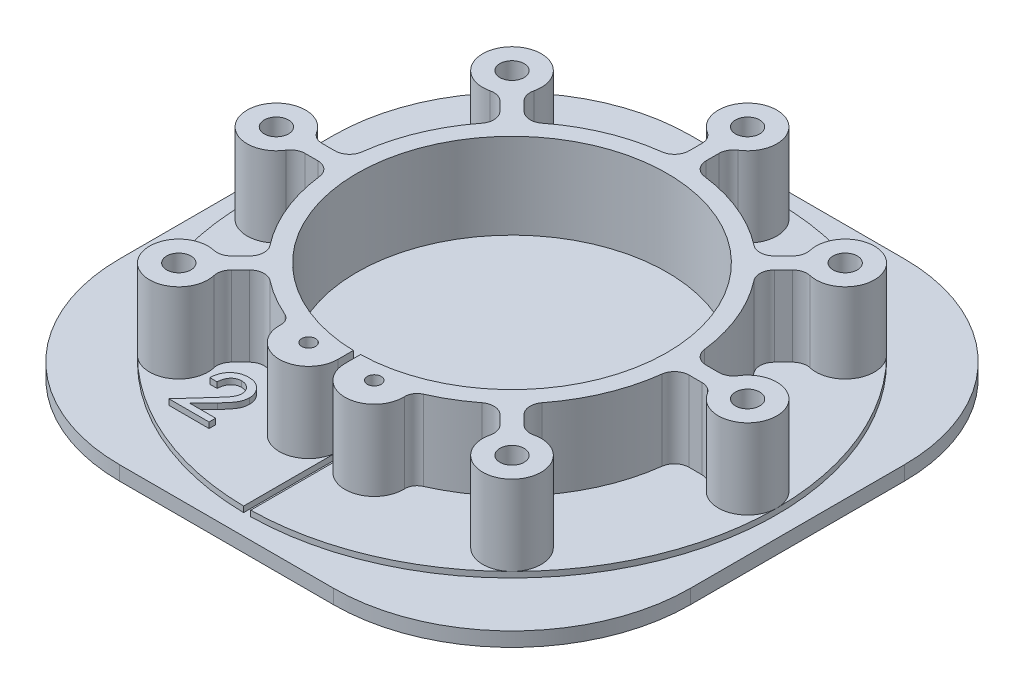
SolidWorks part; units mm, degrees
other "rim"
other "bottom"
ref_plane "Front Plane" through (0, 0, 0) normal (0, 0, 1) x (1, 0, 0)
ref_plane "Top Plane" through (0, 0, 0) normal (0, 1, 0) x (1, 0, 0)
ref_plane "Right Plane" through (0, 0, 0) normal (1, 0, 0) x (0, 0, -1)
ref_axis "Axis1" through (0, -8, 0) along (0, 1, 0)
ref_plane "Plane1" through (0, -11, 0) normal (0, -1, 0) x (-1, 0, 0)
sketch "Sketch1" plane through (0, -11, 0) normal (0, -1, 0) x (-1, 0, 0)
  line L1 (-40, -40) -> (40, -40)
  line L2 (-40, -40) -> (-40, 40)
  line L3 (-40, 40) -> (40, 40)
  line L4 (40, -40) -> (40, 40)
  line L5 (0, 40) -> (0, -40) construction
  line L6 (-40, 0) -> (40, 0) construction
  circle A0 centre (-8, 8) radius 2.25 construction
  circle A1 centre (8, 8) radius 2.25 construction
  circle A2 centre (8, -8) radius 2.25 construction
  circle A3 centre (-8, -8) radius 2.25 construction
  point P0 (0, 0)
  dimension "D2" = 4.5
  dimension "D1" = 80
extrude "Boss-Extrude1" add sketch "Sketch1" along normal blind 2
sketch "Sketch2" plane through (0, -11, 0) normal (0, 1, 0) x (1, 0, 0)
  line L0 (-0.5, -21.7443) -> (-0.5, -23.9116)
  line L1 (0.5, -21.7443) -> (0.5, -23.9116)
  line L2 (-0.5, -21.7443) -> (0.5, -21.7443) construction
  line L3 (0, -1000) -> (0, 49000) construction
  line L4 (-1.2, 27.8087) -> (-1.2, 26.0239)
  line L5 (1.2, 27.8087) -> (1.2, 26.0239)
  line L7 (-20.5122, 18.8152) -> (-19.2502, 17.5531)
  line L8 (-18.8152, 20.5122) -> (-17.5531, 19.2502)
  line L9 (-27.8087, -1.2) -> (-26.0239, -1.2)
  line L10 (-27.8087, 1.2) -> (-26.0239, 1.2)
  line L11 (-18.8152, -20.5122) -> (-17.5531, -19.2502)
  line L12 (-20.5122, -18.8152) -> (-19.2502, -17.5531)
  line L13 (40, 0) -> (-40, 0) construction
  line L14 (18.8152, -20.5122) -> (17.5531, -19.2502)
  line L15 (20.5122, -18.8152) -> (19.2502, -17.5531)
  line L16 (1.2, 27.8087) -> (1.2, 26.0239)
  line L17 (0.5, -21.7443) -> (0.5, -23.9116)
  line L18 (27.8087, 1.2) -> (26.0239, 1.2)
  line L19 (27.8087, -1.2) -> (26.0239, -1.2)
  line L20 (18.8152, 20.5122) -> (17.5531, 19.2502)
  line L21 (20.5122, 18.8152) -> (19.2502, 17.5531)
  circle A0 centre (0, 0) radius 21.75 construction
  arc A1 (-0.5, -21.7443) -> (0.5, -21.7443) centre (0, 0) cw
  circle A3 centre (-4.6, -23.9116) radius 1.7 construction
  circle A4 centre (-4.6, -23.9116) radius 4.1 construction
  arc A5 (-0.5, -23.9116) -> (-8.6972, -23.76) centre (-4.6, -23.9116) cw
  arc A6 (-8.6972, -23.76) -> (-9.7121, -22.142) centre (-10.3942, -23.6972) ccw
  arc A7 (-2.1658, 29.547) -> (2.1658, 29.547) centre (0, 33.0283) cw
  circle A8 centre (0, 33.0283) radius 1.7
  arc A9 (-2.1658, 29.547) -> (-1.2, 27.8087) centre (-3.2473, 27.8087) cw
  arc A10 (2.1658, 29.547) -> (1.2, 27.8087) centre (3.2473, 27.8087) ccw
  arc A11 (-1.2, 26.0239) -> (-2.9938, 23.9923) centre (-3.2473, 26.0239) cw
  arc A12 (1.2, 26.0239) -> (2.9938, 23.9923) centre (3.2473, 26.0239) ccw
  arc A13 (-22.4244, 19.3614) -> (-19.3614, 22.4244) centre (-23.3545, 23.3545) cw
  circle A14 centre (-23.3545, 23.3545) radius 1.7
  arc A15 (-22.4244, 19.3614) -> (-20.5122, 18.8152) centre (-21.9599, 17.3675) cw
  arc A16 (-19.3614, 22.4244) -> (-18.8152, 20.5122) centre (-17.3675, 21.9599) ccw
  arc A17 (-19.2502, 17.5531) -> (-19.0821, 14.8482) centre (-20.6979, 16.1055) cw
  arc A18 (-17.5531, 19.2502) -> (-14.8482, 19.0821) centre (-16.1055, 20.6979) ccw
  arc A19 (-29.547, -2.1658) -> (-29.547, 2.1658) centre (-33.0283, 0) cw
  circle A20 centre (-33.0283, 0) radius 1.7
  arc A21 (-29.547, -2.1658) -> (-27.8087, -1.2) centre (-27.8087, -3.2473) cw
  arc A22 (-29.547, 2.1658) -> (-27.8087, 1.2) centre (-27.8087, 3.2473) ccw
  arc A23 (-26.0239, -1.2) -> (-23.9923, -2.9938) centre (-26.0239, -3.2473) cw
  arc A24 (-26.0239, 1.2) -> (-23.9923, 2.9938) centre (-26.0239, 3.2473) ccw
  arc A25 (-19.3614, -22.4244) -> (-22.4244, -19.3614) centre (-23.3545, -23.3545) cw
  circle A26 centre (-23.3545, -23.3545) radius 1.7
  arc A27 (-19.3614, -22.4244) -> (-18.8152, -20.5122) centre (-17.3675, -21.9599) cw
  arc A28 (-22.4244, -19.3614) -> (-20.5122, -18.8152) centre (-21.9599, -17.3675) ccw
  arc A29 (-17.5531, -19.2502) -> (-14.8482, -19.0821) centre (-16.1055, -20.6979) cw
  arc A30 (-19.2502, -17.5531) -> (-19.0821, -14.8482) centre (-20.6979, -16.1055) ccw
  arc A31 (-2.9938, 23.9923) -> (-14.8482, 19.0821) centre (0, 0) ccw
  arc A32 (-19.0821, 14.8482) -> (-23.9923, 2.9938) centre (0, 0) ccw
  arc A33 (-23.9923, -2.9938) -> (-19.0821, -14.8482) centre (0, 0) ccw
  arc A34 (-14.8482, -19.0821) -> (-9.7121, -22.142) centre (0, 0) ccw
  arc A35 (19.3614, -22.4244) -> (18.8152, -20.5122) centre (17.3675, -21.9599) ccw
  arc A36 (17.5531, -19.2502) -> (14.8482, -19.0821) centre (16.1055, -20.6979) ccw
  arc A37 (19.2502, -17.5531) -> (19.0821, -14.8482) centre (20.6979, -16.1055) cw
  arc A38 (22.4244, -19.3614) -> (20.5122, -18.8152) centre (21.9599, -17.3675) cw
  arc A39 (2.1658, 29.547) -> (1.2, 27.8087) centre (3.2473, 27.8087) ccw
  arc A40 (1.2, 26.0239) -> (2.9938, 23.9923) centre (3.2473, 26.0239) ccw
  arc A41 (2.9938, 23.9923) -> (14.8482, 19.0821) centre (0, 0) cw
  arc A42 (14.8482, -19.0821) -> (9.7121, -22.142) centre (0, 0) cw
  arc A43 (8.6972, -23.76) -> (9.7121, -22.142) centre (10.3942, -23.6972) cw
  arc A44 (0.5, -23.9116) -> (8.6972, -23.76) centre (4.6, -23.9116) ccw
  circle A45 centre (4.6, -23.9116) radius 1.7 construction
  arc A46 (23.9923, -2.9938) -> (19.0821, -14.8482) centre (0, 0) cw
  arc A47 (19.0821, 14.8482) -> (23.9923, 2.9938) centre (0, 0) cw
  arc A48 (19.3614, -22.4244) -> (22.4244, -19.3614) centre (23.3545, -23.3545) ccw
  arc A49 (26.0239, 1.2) -> (23.9923, 2.9938) centre (26.0239, 3.2473) cw
  arc A50 (26.0239, -1.2) -> (23.9923, -2.9938) centre (26.0239, -3.2473) ccw
  arc A51 (29.547, 2.1658) -> (27.8087, 1.2) centre (27.8087, 3.2473) cw
  arc A52 (29.547, -2.1658) -> (27.8087, -1.2) centre (27.8087, -3.2473) ccw
  circle A53 centre (33.0283, 0) radius 1.7
  arc A54 (29.547, -2.1658) -> (29.547, 2.1658) centre (33.0283, 0) ccw
  arc A55 (17.5531, 19.2502) -> (14.8482, 19.0821) centre (16.1055, 20.6979) cw
  arc A56 (19.2502, 17.5531) -> (19.0821, 14.8482) centre (20.6979, 16.1055) ccw
  arc A57 (19.3614, 22.4244) -> (18.8152, 20.5122) centre (17.3675, 21.9599) cw
  arc A58 (22.4244, 19.3614) -> (20.5122, 18.8152) centre (21.9599, 17.3675) ccw
  circle A59 centre (23.3545, 23.3545) radius 1.7
  arc A60 (22.4244, 19.3614) -> (19.3614, 22.4244) centre (23.3545, 23.3545) ccw
  circle A61 centre (23.3545, -23.3545) radius 1.7
  circle A62 centre (-4.6, -23.9116) radius 0.9685
  circle A63 centre (4.6, -23.9116) radius 0.9685
  point P79 (0, 0)
  dimension "D1" = 43.5
  dimension "D4" = 3.4
  dimension "D3" = 1.937
  dimension "D2" = 1
  dimension "D7" = 2.4
  dimension "D8" = 4
extrude "Boss-Extrude2" add sketch "Sketch2" along normal offset from surface (12 mm away) 1 separate body contours A58 A60 A57 L20 A55 A41 A12 L5 A10 A7 A9 L4 A11 A31 A18 L8 A16 A13 A15 L7 A17 A32 A24 L10 A22 A19 A21 L9 A23 A33 A30 L12 A28 A25 A27 L11 A29 A34 A6 A5 L0 A1 L1 A44 A43 A42 A36 L14 A35 A48 A38 region at (-1.4878, -11, 22.8279) offset beyond the face yes
sketch "Sketch3" plane through (0, -11, 0) normal (0, 1, 0) x (1, 0, 0)
  circle A0 centre (0, 33.0283) radius 1.4
  circle A1 centre (23.3545, 23.3545) radius 1.4
  circle A2 centre (33.0283, 0) radius 1.4
  circle A3 centre (23.3545, -23.3545) radius 1.4
  circle A4 centre (4.6, -23.9116) radius 1.4
  circle A5 centre (-4.6, -23.9116) radius 1.4
  circle A6 centre (-23.3545, -23.3545) radius 1.4
  circle A7 centre (-33.0283, 0) radius 1.4
  circle A8 centre (-23.3545, 23.3545) radius 1.4
  dimension "D1" = 2.8
extrude "Cut-Extrude1" cut sketch "Sketch3" against normal through all
fillet "Fillet1" radius 25 4 edges at (-40, -12, -40) (40, -12, -40) (40, -12, 40) (-40, -12, 40)
sketch "Sketch4" plane through (0, -11, 0) normal (0, 1, 0) x (1, 0, 0)
  line L32 (18.5323, 20.7951) -> (17.2703, 19.533)
  line L33 (1.6, 26.0239) -> (1.6, 27.8087)
  line L34 (-1.6, 27.8087) -> (-1.6, 26.0239)
  line L35 (-17.2703, 19.533) -> (-18.5323, 20.7951)
  line L36 (-20.7951, 18.5323) -> (-19.533, 17.2703)
  line L37 (-26.0239, 1.6) -> (-27.8087, 1.6)
  line L38 (-27.8087, -1.6) -> (-26.0239, -1.6)
  line L39 (-19.533, -17.2703) -> (-20.7951, -18.5323)
  line L40 (-18.5323, -20.7951) -> (-17.2703, -19.533)
  line L41 (17.2703, -19.533) -> (18.5323, -20.7951)
  line L42 (20.7951, -18.5323) -> (19.533, -17.2703)
  line L43 (26.0239, -1.6) -> (27.8087, -1.6)
  line L44 (27.8087, 1.6) -> (26.0239, 1.6)
  line L45 (19.533, 17.2703) -> (20.7951, 18.5323)
  line L46 (18.5323, 20.7951) -> (17.2703, 19.533)
  line L47 (1.6, 26.0239) -> (1.6, 27.8087)
  line L48 (-1.6, 27.8087) -> (-1.6, 26.0239)
  line L49 (-17.2703, 19.533) -> (-18.5323, 20.7951)
  line L50 (-20.7951, 18.5323) -> (-19.533, 17.2703)
  line L51 (-26.0239, 1.6) -> (-27.8087, 1.6)
  line L52 (-27.8087, -1.6) -> (-26.0239, -1.6)
  line L53 (-19.533, -17.2703) -> (-20.7951, -18.5323)
  line L54 (-18.5323, -20.7951) -> (-17.2703, -19.533)
  line L55 (17.2703, -19.533) -> (18.5323, -20.7951)
  line L56 (20.7951, -18.5323) -> (19.533, -17.2703)
  line L57 (26.0239, -1.6) -> (27.8087, -1.6)
  line L58 (27.8087, 1.6) -> (26.0239, 1.6)
  line L59 (19.533, 17.2703) -> (20.7951, 18.5323)
  line L60 (-0.1, -23.9116) -> (-0.1, -21.3498)
  line L61 (-0.1, -23.9116) -> (-0.1, -21.3498)
  line L62 (0.1, -21.3498) -> (0.1, -23.9116)
  line L63 (0.1, -21.3498) -> (0.1, -23.9116)
  arc A96 (22.3336, 18.9719) -> (20.7951, 18.5323) centre (21.9599, 17.3675) ccw
  arc A97 (22.3336, 18.9719) -> (18.9719, 22.3336) centre (23.3545, 23.3545) ccw
  arc A98 (18.5323, 20.7951) -> (18.9719, 22.3336) centre (17.3675, 21.9599) ccw
  arc A99 (15.0938, 19.3978) -> (17.2703, 19.533) centre (16.1055, 20.6979) ccw
  arc A100 (15.0938, 19.3978) -> (3.0434, 24.3892) centre (0, 0) ccw
  arc A101 (1.6, 26.0239) -> (3.0434, 24.3892) centre (3.2473, 26.0239) ccw
  arc A102 (2.3771, 29.2074) -> (1.6, 27.8087) centre (3.2473, 27.8087) ccw
  arc A103 (2.3771, 29.2074) -> (-2.3771, 29.2074) centre (0, 33.0283) ccw
  arc A104 (-1.6, 27.8087) -> (-2.3771, 29.2074) centre (-3.2473, 27.8087) ccw
  arc A105 (-3.0434, 24.3892) -> (-1.6, 26.0239) centre (-3.2473, 26.0239) ccw
  arc A106 (-3.0434, 24.3892) -> (-15.0938, 19.3978) centre (0, 0) ccw
  arc A107 (-17.2703, 19.533) -> (-15.0938, 19.3978) centre (-16.1055, 20.6979) ccw
  arc A108 (-18.9719, 22.3336) -> (-18.5323, 20.7951) centre (-17.3675, 21.9599) ccw
  arc A109 (-18.9719, 22.3336) -> (-22.3336, 18.9719) centre (-23.3545, 23.3545) ccw
  arc A110 (-20.7951, 18.5323) -> (-22.3336, 18.9719) centre (-21.9599, 17.3675) ccw
  arc A111 (-19.3978, 15.0938) -> (-19.533, 17.2703) centre (-20.6979, 16.1055) ccw
  arc A112 (-19.3978, 15.0938) -> (-24.3892, 3.0434) centre (0, 0) ccw
  arc A113 (-26.0239, 1.6) -> (-24.3892, 3.0434) centre (-26.0239, 3.2473) ccw
  arc A114 (-29.2074, 2.3771) -> (-27.8087, 1.6) centre (-27.8087, 3.2473) ccw
  arc A115 (-29.2074, 2.3771) -> (-29.2074, -2.3771) centre (-33.0283, 0) ccw
  arc A116 (-27.8087, -1.6) -> (-29.2074, -2.3771) centre (-27.8087, -3.2473) ccw
  arc A117 (-24.3892, -3.0434) -> (-26.0239, -1.6) centre (-26.0239, -3.2473) ccw
  arc A118 (-24.3892, -3.0434) -> (-19.3978, -15.0938) centre (0, 0) ccw
  arc A119 (-19.533, -17.2703) -> (-19.3978, -15.0938) centre (-20.6979, -16.1055) ccw
  arc A120 (-22.3336, -18.9719) -> (-20.7951, -18.5323) centre (-21.9599, -17.3675) ccw
  arc A121 (-22.3336, -18.9719) -> (-18.9719, -22.3336) centre (-23.3545, -23.3545) ccw
  arc A122 (-18.5323, -20.7951) -> (-18.9719, -22.3336) centre (-17.3675, -21.9599) ccw
  arc A123 (-15.0938, -19.3978) -> (-17.2703, -19.533) centre (-16.1055, -20.6979) ccw
  arc A124 (-15.0938, -19.3978) -> (-9.8727, -22.5084) centre (0, 0) ccw
  arc A125 (-9.0969, -23.7452) -> (-9.8727, -22.5084) centre (-10.3942, -23.6972) ccw
  arc A126 (-9.0969, -23.7452) -> (-0.1, -23.9116) centre (-4.6, -23.9116) ccw
  arc A127 (0.1, -23.9116) -> (9.0969, -23.7452) centre (4.6, -23.9116) ccw
  arc A128 (9.8727, -22.5084) -> (9.0969, -23.7452) centre (10.3942, -23.6972) ccw
  arc A129 (9.8727, -22.5084) -> (15.0938, -19.3978) centre (0, 0) ccw
  arc A130 (17.2703, -19.533) -> (15.0938, -19.3978) centre (16.1055, -20.6979) ccw
  arc A131 (18.9719, -22.3336) -> (18.5323, -20.7951) centre (17.3675, -21.9599) ccw
  arc A132 (18.9719, -22.3336) -> (22.3336, -18.9719) centre (23.3545, -23.3545) ccw
  arc A133 (20.7951, -18.5323) -> (22.3336, -18.9719) centre (21.9599, -17.3675) ccw
  arc A134 (19.3978, -15.0938) -> (19.533, -17.2703) centre (20.6979, -16.1055) ccw
  arc A135 (19.3978, -15.0938) -> (24.3892, -3.0434) centre (0, 0) ccw
  arc A136 (26.0239, -1.6) -> (24.3892, -3.0434) centre (26.0239, -3.2473) ccw
  arc A137 (29.2074, -2.3771) -> (27.8087, -1.6) centre (27.8087, -3.2473) ccw
  arc A138 (29.2074, -2.3771) -> (29.2074, 2.3771) centre (33.0283, 0) ccw
  arc A139 (27.8087, 1.6) -> (29.2074, 2.3771) centre (27.8087, 3.2473) ccw
  arc A140 (24.3892, 3.0434) -> (26.0239, 1.6) centre (26.0239, 3.2473) ccw
  arc A141 (24.3892, 3.0434) -> (19.3978, 15.0938) centre (0, 0) ccw
  arc A142 (19.533, 17.2703) -> (19.3978, 15.0938) centre (20.6979, 16.1055) ccw
  arc A143 (22.3336, 18.9719) -> (20.7951, 18.5323) centre (21.9599, 17.3675) ccw
  arc A144 (22.3336, 18.9719) -> (18.9719, 22.3336) centre (23.3545, 23.3545) ccw
  arc A145 (18.5323, 20.7951) -> (18.9719, 22.3336) centre (17.3675, 21.9599) ccw
  arc A146 (15.0938, 19.3978) -> (17.2703, 19.533) centre (16.1055, 20.6979) ccw
  arc A147 (15.0938, 19.3978) -> (3.0434, 24.3892) centre (0, 0) ccw
  arc A148 (1.6, 26.0239) -> (3.0434, 24.3892) centre (3.2473, 26.0239) ccw
  arc A149 (2.3771, 29.2074) -> (1.6, 27.8087) centre (3.2473, 27.8087) ccw
  arc A150 (2.3771, 29.2074) -> (-2.3771, 29.2074) centre (0, 33.0283) ccw
  arc A151 (-1.6, 27.8087) -> (-2.3771, 29.2074) centre (-3.2473, 27.8087) ccw
  arc A152 (-3.0434, 24.3892) -> (-1.6, 26.0239) centre (-3.2473, 26.0239) ccw
  arc A153 (-3.0434, 24.3892) -> (-15.0938, 19.3978) centre (0, 0) ccw
  arc A154 (-17.2703, 19.533) -> (-15.0938, 19.3978) centre (-16.1055, 20.6979) ccw
  arc A155 (-18.9719, 22.3336) -> (-18.5323, 20.7951) centre (-17.3675, 21.9599) ccw
  arc A156 (-18.9719, 22.3336) -> (-22.3336, 18.9719) centre (-23.3545, 23.3545) ccw
  arc A157 (-20.7951, 18.5323) -> (-22.3336, 18.9719) centre (-21.9599, 17.3675) ccw
  arc A158 (-19.3978, 15.0938) -> (-19.533, 17.2703) centre (-20.6979, 16.1055) ccw
  arc A159 (-19.3978, 15.0938) -> (-24.3892, 3.0434) centre (0, 0) ccw
  arc A160 (-26.0239, 1.6) -> (-24.3892, 3.0434) centre (-26.0239, 3.2473) ccw
  arc A161 (-29.2074, 2.3771) -> (-27.8087, 1.6) centre (-27.8087, 3.2473) ccw
  arc A162 (-29.2074, 2.3771) -> (-29.2074, -2.3771) centre (-33.0283, 0) ccw
  arc A163 (-27.8087, -1.6) -> (-29.2074, -2.3771) centre (-27.8087, -3.2473) ccw
  arc A164 (-24.3892, -3.0434) -> (-26.0239, -1.6) centre (-26.0239, -3.2473) ccw
  arc A165 (-24.3892, -3.0434) -> (-19.3978, -15.0938) centre (0, 0) ccw
  arc A166 (-19.533, -17.2703) -> (-19.3978, -15.0938) centre (-20.6979, -16.1055) ccw
  arc A167 (-22.3336, -18.9719) -> (-20.7951, -18.5323) centre (-21.9599, -17.3675) ccw
  arc A168 (-22.3336, -18.9719) -> (-18.9719, -22.3336) centre (-23.3545, -23.3545) ccw
  arc A169 (-18.5323, -20.7951) -> (-18.9719, -22.3336) centre (-17.3675, -21.9599) ccw
  arc A170 (-15.0938, -19.3978) -> (-17.2703, -19.533) centre (-16.1055, -20.6979) ccw
  arc A171 (-15.0938, -19.3978) -> (-9.8727, -22.5084) centre (0, 0) ccw
  arc A172 (-9.0969, -23.7452) -> (-9.8727, -22.5084) centre (-10.3942, -23.6972) ccw
  arc A173 (-9.0969, -23.7452) -> (-0.1, -23.9116) centre (-4.6, -23.9116) ccw
  arc A174 (0.1, -23.9116) -> (9.0969, -23.7452) centre (4.6, -23.9116) ccw
  arc A175 (9.8727, -22.5084) -> (9.0969, -23.7452) centre (10.3942, -23.6972) ccw
  arc A176 (9.8727, -22.5084) -> (15.0938, -19.3978) centre (0, 0) ccw
  arc A177 (17.2703, -19.533) -> (15.0938, -19.3978) centre (16.1055, -20.6979) ccw
  arc A178 (18.9719, -22.3336) -> (18.5323, -20.7951) centre (17.3675, -21.9599) ccw
  arc A179 (18.9719, -22.3336) -> (22.3336, -18.9719) centre (23.3545, -23.3545) ccw
  arc A180 (20.7951, -18.5323) -> (22.3336, -18.9719) centre (21.9599, -17.3675) ccw
  arc A181 (19.3978, -15.0938) -> (19.533, -17.2703) centre (20.6979, -16.1055) ccw
  arc A182 (19.3978, -15.0938) -> (24.3892, -3.0434) centre (0, 0) ccw
  arc A183 (26.0239, -1.6) -> (24.3892, -3.0434) centre (26.0239, -3.2473) ccw
  arc A184 (29.2074, -2.3771) -> (27.8087, -1.6) centre (27.8087, -3.2473) ccw
  arc A185 (29.2074, -2.3771) -> (29.2074, 2.3771) centre (33.0283, 0) ccw
  arc A186 (27.8087, 1.6) -> (29.2074, 2.3771) centre (27.8087, 3.2473) ccw
  arc A187 (24.3892, 3.0434) -> (26.0239, 1.6) centre (26.0239, 3.2473) ccw
  arc A188 (24.3892, 3.0434) -> (19.3978, 15.0938) centre (0, 0) ccw
  arc A189 (19.533, 17.2703) -> (19.3978, 15.0938) centre (20.6979, 16.1055) ccw
  arc A190 (0.1, -21.3498) -> (-0.1, -21.3498) centre (0, 0) ccw
  arc A191 (0.1, -21.3498) -> (-0.1, -21.3498) centre (0, 0) ccw
  dimension "D1" = 0.4
sketch "Sketch5" plane through (0, -11, 0) normal (0, -1, 0) x (1, 0, 0)
  circle A144 centre (0, 0) radius 37.1283
  arc A145 (-2.1658, -29.547) -> (2.1658, -29.547) centre (0, -33.0283) ccw construction
  circle A146 centre (-23.3545, 23.3545) radius 1.7 construction
  circle A147 centre (-23.3545, 23.3545) radius 1.7
  circle A148 centre (-4.6, 23.9116) radius 1.7 construction
  circle A149 centre (4.6, 23.9116) radius 1.7 construction
  circle A150 centre (23.3545, 23.3545) radius 1.7 construction
  circle A151 centre (33.0283, 0) radius 1.7 construction
  circle A152 centre (23.3545, -23.3545) radius 1.7 construction
  circle A153 centre (0, -33.0283) radius 1.7 construction
  circle A154 centre (-23.3545, -23.3545) radius 1.7 construction
  circle A155 centre (-33.0283, 0) radius 1.7 construction
  circle A156 centre (-4.6, 23.9116) radius 1.7
  circle A157 centre (4.6, 23.9116) radius 1.7
  circle A158 centre (23.3545, 23.3545) radius 1.7
  circle A159 centre (33.0283, 0) radius 1.7
  circle A160 centre (23.3545, -23.3545) radius 1.7
  circle A161 centre (0, -33.0283) radius 1.7
  circle A162 centre (-23.3545, -23.3545) radius 1.7
  circle A163 centre (-33.0283, 0) radius 1.7
  circle A164 centre (0, 0) radius 21.75
  arc A165 (-0.5, 21.7443) -> (0.5, 21.7443) centre (0, 0) ccw construction
extrude "Boss-Extrude3" add sketch "Sketch5" against normal blind 0.8
sketch "Sketch6" plane through (0, -10.2, 0) normal (0, 1, 0) x (1, 0, 0)
  line L0 (0, -201000) -> (0, 249000) construction
  line L1 (-0.5, -37.1283) -> (0.5, -37.1283)
  line L2 (-0.5, -37.1283) -> (-0.5, -21.7443)
  line L3 (-0.5, -21.7443) -> (0.5, -21.7443)
  line L4 (0.5, -37.1283) -> (0.5, -21.7443)
  line L5 (0, -21.7443) -> (0, -37.1283) construction
  line L6 (-0.5, -29.4363) -> (0.5, -29.4363) construction
  circle A0 centre (0, 0) radius 37.1283 construction
  point P0 (0, -29.4363)
extrude "Cut-Extrude2" cut sketch "Sketch6" against normal through all
sketch "Sketch7" plane through (0, -10.2, 0) normal (0, 1, 0) x (1, 0, 0)
  text T0 "<b>2</b>" font "Century Gothic" height 8
extrude "Boss-Extrude4" add sketch "Sketch7" along normal blind 0.8
